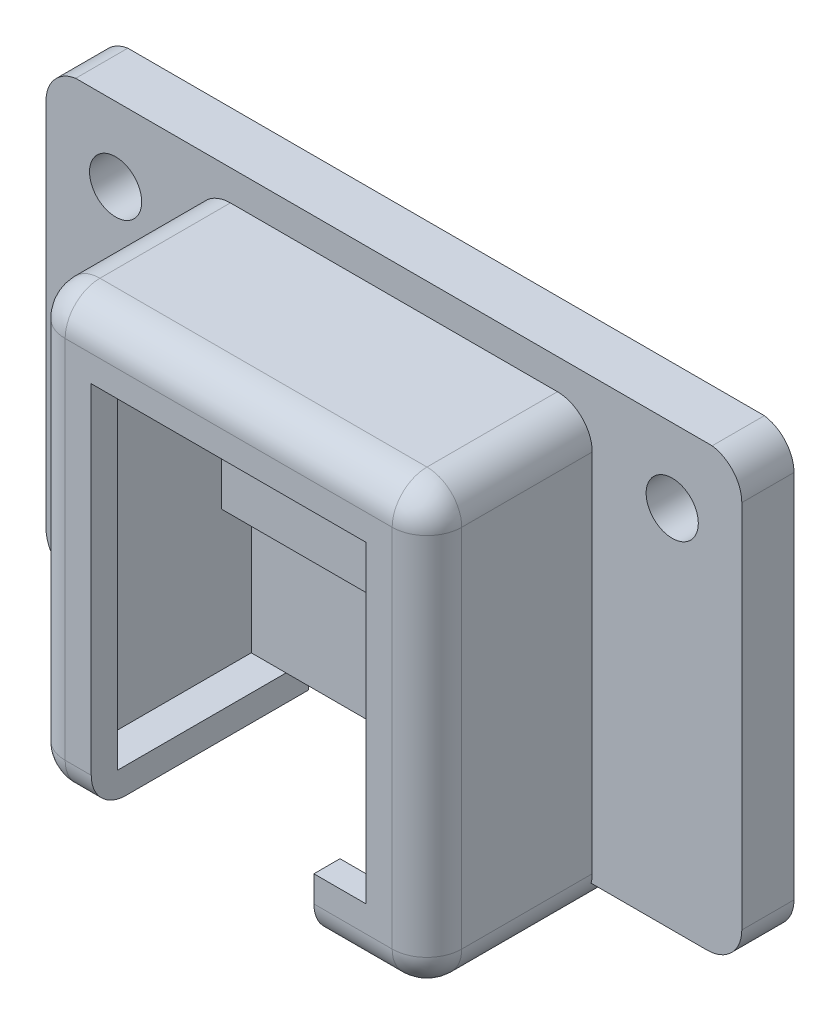
SolidWorks part; units mm, degrees
ref_plane "Alzado" through (0, 0, 0) normal (0, 0, 1) x (1, 0, 0)
ref_plane "Planta" through (0, 0, 0) normal (0, 1, 0) x (1, 0, 0)
ref_plane "Vista lateral" through (0, 0, 0) normal (1, 0, 0) x (0, 0, -1)
sketch "Croquis1" plane through (0, 0, 0) normal (0, 0, 1) x (1, 0, 0)
  line L2 (-75.3066, 17.9596) -> (-75.3066, -5.318)
  line L3 (-75.3066, -5.318) -> (-35.3066, -5.318)
  line L4 (-35.3066, 17.9596) -> (-35.3066, -5.318)
  line L6 (-55.3066, 22.682) -> (-35.3066, 22.682) construction
  line L8 (-73.6033, 19.9375) -> (-37.0099, 19.9375)
  circle A0 centre (-71.3066, 15.682) radius 1.5
  circle A1 centre (-39.3066, 15.682) radius 1.5
  arc A2 (-37.0099, 19.9375) -> (-35.3066, 17.9596) centre (-37.3066, 17.9596) cw
  arc A4 (-73.6033, 19.9375) -> (-75.3066, 17.9596) centre (-73.3066, 17.9596) ccw
  point P17 (-75.3066, 19.682)
  dimension "D3" = 2
  dimension "D4" = 32
  dimension "D5" = 3
  dimension "D6" = 3
  dimension "D1" = 7
  dimension "D2" = 3
  dimension "D7" = 4
extrude "Saliente-Extruir1" add sketch "Croquis1" along normal blind 3
sketch "Croquis2" plane through (0, 0, 3) normal (0, 0, 1) x (1, 0, 0)
  line L0 (-75.3066, -5.318) -> (-35.3066, -5.318) construction
  line L1 (-66.7066, -5.318) -> (-65.2066, -5.318)
  line L2 (-66.7066, -5.318) -> (-66.7066, 18.182)
  line L3 (-66.7066, 18.182) -> (-43.9066, 18.182)
  line L4 (-43.9066, -5.318) -> (-43.9066, 18.182)
  line L5 (-45.4066, -5.318) -> (-43.9066, -5.318)
  line L6 (-65.2066, 16.682) -> (-45.4066, 16.682)
  line L7 (-65.2066, 16.682) -> (-65.2066, -5.318)
  line L9 (-45.4066, 16.682) -> (-45.4066, -5.318)
  dimension "D1" = 22.8
  dimension "D3" = 23.5
  dimension "D4" = 1.5
  dimension "D5" = 1.5
  dimension "D6" = 1.5
extrude "Saliente-Extruir2" add sketch "Croquis2" along normal blind 8
sketch "Croquis3" plane through (0, -5.318, 0) normal (0, -1, 0) x (1, 0, 0)
  line L1 (-65.2066, 3) -> (-52.2066, 3)
  line L2 (-65.2066, 3) -> (-65.2066, 1.3)
  line L3 (-65.2066, 1.3) -> (-52.2066, 1.3)
  line L4 (-52.2066, 3) -> (-52.2066, 1.3)
  dimension "D1" = 13
  dimension "D2" = 1.7
extrude "Cortar-Extruir1" cut sketch "Croquis3" against normal blind 8
sketch "Croquis5" plane through (0, -5.318, 0) normal (0, -1, 0) x (1, 0, 0)
  line L0 (-75.3066, 0) -> (-35.3066, 0) construction
  line L1 (-66.7066, 11) -> (-63.2066, 11)
  line L2 (-66.7066, 11) -> (-66.7066, 0)
  line L3 (-66.7066, 0) -> (-63.2066, 0)
  line L4 (-63.2066, 11) -> (-63.2066, 0)
  line L5 (-45.4066, 11) -> (-45.4066, 3) construction
  line L6 (-43.9066, 11) -> (-50.4066, 11)
  line L7 (-43.9066, 11) -> (-43.9066, 0)
  line L8 (-43.9066, 0) -> (-50.4066, 0)
  line L9 (-50.4066, 11) -> (-50.4066, 0)
  line L10 (-65.2066, 11) -> (-65.2066, 1.3) construction
  dimension "D1" = 5
  dimension "D2" = 2
extrude "Saliente-Extruir3" add sketch "Croquis5" along normal blind 1.5
sketch "Croquis6" plane through (0, 0, 11) normal (0, 0, 1) x (1, 0, 0)
  line L0 (-63.2066, -5.318) -> (-63.2066, -6.818)
  line L1 (-63.2066, -6.818) -> (-66.7066, -6.818)
  line L2 (-66.7066, -6.818) -> (-66.7066, 18.182)
  line L3 (-66.7066, 18.182) -> (-43.9066, 18.182)
  line L4 (-43.9066, 18.182) -> (-43.9066, -6.818)
  line L5 (-43.9066, -6.818) -> (-50.4066, -6.818)
  line L6 (-50.4066, -6.818) -> (-50.4066, -3.318)
  line L7 (-50.4066, -3.318) -> (-47.4066, -3.318)
  line L8 (-47.4066, -3.318) -> (-47.4066, 14.682)
  line L9 (-47.4066, 14.682) -> (-63.2066, 14.682)
  line L10 (-63.2066, 14.682) -> (-63.2066, -5.318)
  dimension "D1" = 15.8
extrude "Saliente-Extruir4" add sketch "Croquis6" along normal blind 1.5
fillet "Redondeo1" radius 2 11 edges at (-43.9066, 18.182, 7.75) (-43.9066, -6.818, 6.25) (-66.7066, 18.182, 7.75) (-66.7066, -6.818, 6.25) (-64.9566, -6.818, 12.5) (-47.1566, -6.818, 12.5) (-43.9066, 5.682, 12.5) (-55.3066, 18.182, 12.5) (-66.7066, 5.682, 12.5) (-35.3066, -5.318, 1.5) (-75.3066, -5.318, 1.5)
